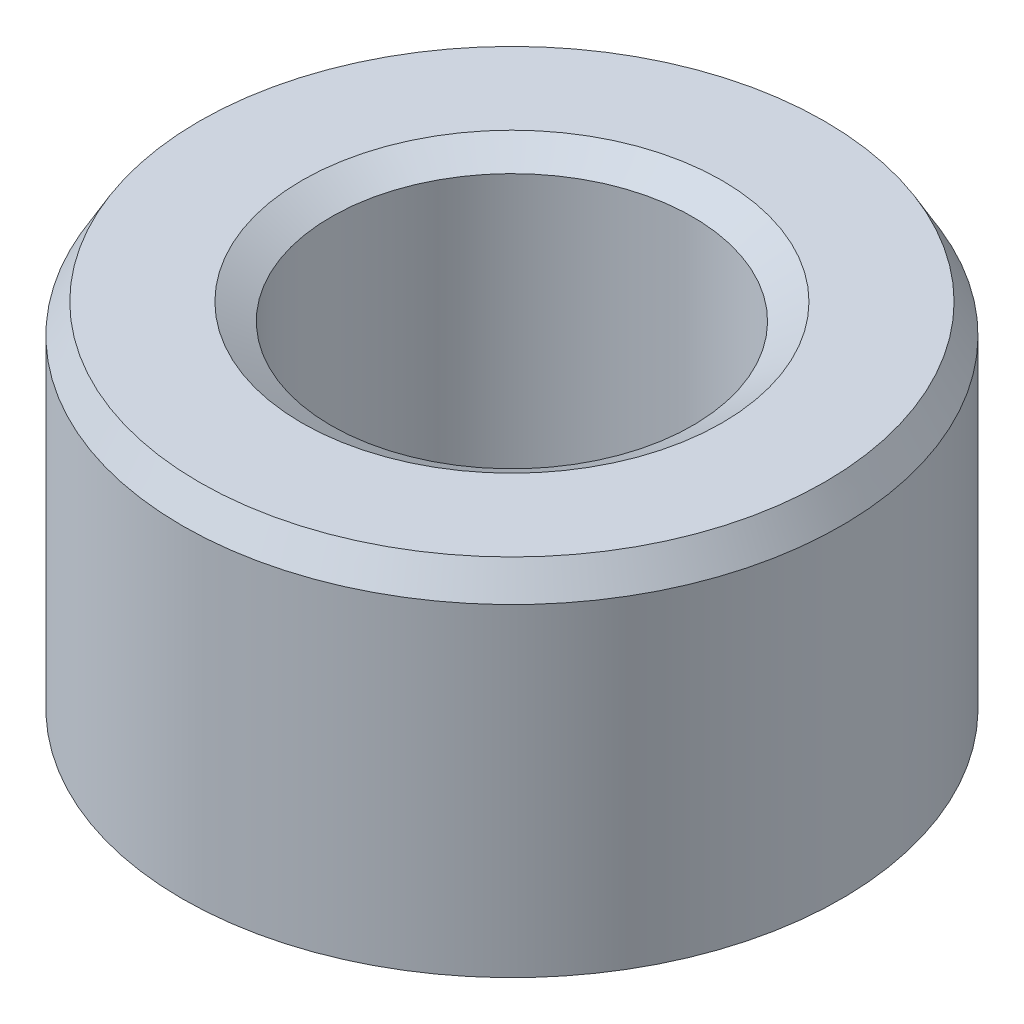
SolidWorks part; units mm, degrees
ref_plane "Front Plane" through (0, 0, 0) normal (0, 0, 1) x (1, 0, 0)
ref_plane "Top Plane" through (0, 0, 0) normal (0, 1, 0) x (1, 0, 0)
ref_plane "Right Plane" through (0, 0, 0) normal (1, 0, 0) x (0, 0, -1)
sketch "Sketch1" plane through (0, 0, 0) normal (0, 1, 0) x (1, 0, 0)
  circle A0 centre (0, 0) radius 37.5
  dimension "SLEEVE_OD" = 75
extrude "Boss-Extrude1" add sketch "Sketch1" along normal blind 42.0188
sketch "Sketch2" plane through (0, 0, 0) normal (0, 1, 0) x (1, 0, 0)
  circle A0 centre (0, 0) radius 20.5702
  dimension "BORE_D" = 41.1404
extrude "Cut-Extrude1" cut sketch "Sketch2" along normal through all
chamfer "Chamfer1" distance 3.3315 angle 30 4 edges at (0, 42.0188, 20.5702) (0, 0, 20.5702) (0, 0, 37.5) (0, 42.0188, 37.5) first distance on face at (0, 42.0188, 20.5702) first distance on face at (0, 0, 20.5702) first distance on face at (0, 42.0188, 37.5)
